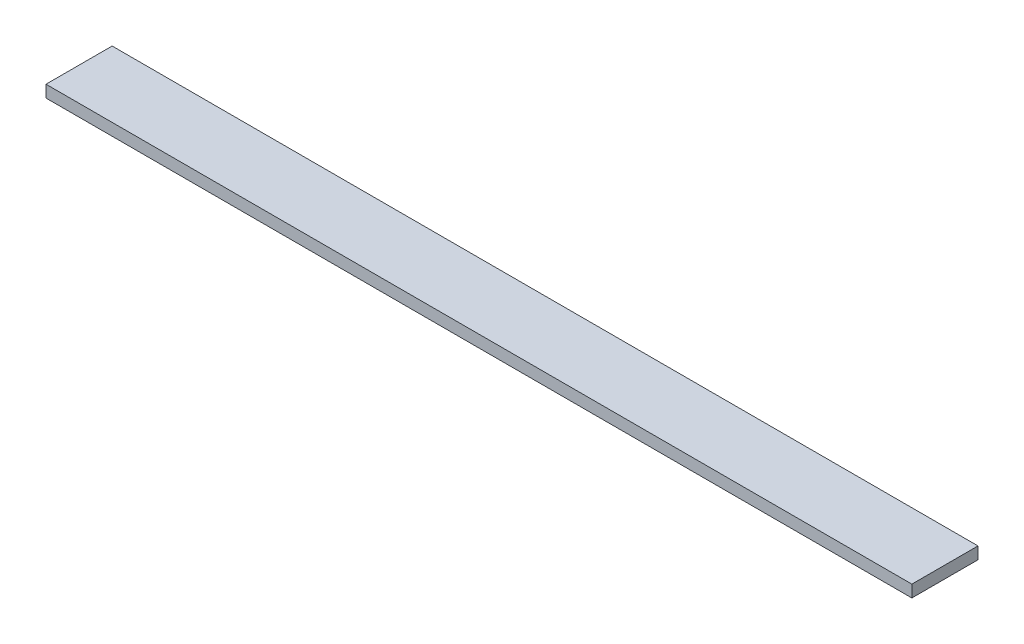
SolidWorks part; units mm, degrees
material "PVC Rigid"
ref_plane "Frontal Plane" through (0, 0, 0) normal (0, 0, 1) x (1, 0, 0)
ref_plane "Horizontal Plane" through (0, 0, 0) normal (0, 1, 0) x (1, 0, 0)
ref_plane "Profile Plane" through (0, 0, 0) normal (1, 0, 0) x (0, 0, -1)
sketch "Sketch1" plane through (0, 0, 0) normal (0, 1, 0) x (1, 0, 0)
  line L1 (-914.4, -69.85) -> (914.4, -69.85)
  line L2 (-914.4, -69.85) -> (-914.4, 69.85)
  line L3 (-914.4, 69.85) -> (914.4, 69.85)
  line L4 (914.4, -69.85) -> (914.4, 69.85)
  line L5 (-914.4, -69.85) -> (914.4, 69.85) construction
  line L6 (-914.4, 69.85) -> (914.4, -69.85) construction
  point P0 (0, 0)
  dimension "D1" = 139.7
  dimension "D2" = 1828.8
extrude "Boss-Extrude1" add sketch "Sketch1" along normal blind 25.4
sketch "Sketch2" plane through (0, 25.4, 0) normal (0, 1, 0) x (1, 0, 0)
  line L0 (-784.4, 69.85) -> (-784.4, -80.15)
  line L1 (914.4, 69.85) -> (-914.4, 69.85) construction
  line L2 (-784.4, -80.15) -> (914.4, -80.15)
  line L3 (914.4, -69.85) -> (914.4, 69.85) construction
  line L4 (914.4, -80.15) -> (914.4, 69.85)
  line L5 (914.4, 69.85) -> (-784.4, 69.85)
  line L6 (-914.4, 69.85) -> (-914.4, -69.85) construction
  dimension "D1" = 130
  dimension "D2" = 150
extrude "Cut-Extrude1" [suppressed] cut sketch "Sketch2" against normal through all
sketch "Sketch3" [suppressed] plane through (0, 12.7, 0) normal (0, 1, 0) x (1, 0, 0)
  line L0 (-720, 155) -> (-850, 155) construction
  line L1 (-830, 135) -> (-740, 135)
  line L2 (-830, 135) -> (-830, 5)
  line L3 (-830, 5) -> (-740, 5)
  line L4 (-740, 135) -> (-740, 5)
  line L5 (-830, 135) -> (-740, 5) construction
  line L6 (-830, 5) -> (-740, 135) construction
  line L7 (-850, 155) -> (-850, -155) construction
  line L8 (-720, 155) -> (-720, 5) construction
  line L9 (-720, 5) -> (850, 5) construction
  point P0 (-785, 70)
  dimension "D1" = 20
  dimension "D2" = 20
  dimension "D3" = 20
extrude "Cut-Extrude2" [suppressed] cut sketch "Sketch3" against normal offset from surface (5 mm away) 5 up to face at (0, 0, 0)
sketch "Sketch4" plane through (0, 25.4, 0) normal (0, 1, 0) x (1, 0, 0)
  line L0 (-914.4, -69.85) -> (914.4, -69.85) construction
  line L1 (768, 38.45) -> (812, 38.45) construction
  line L2 (0, 219.5854) -> (0, -221.9562) construction
  line L3 (-837.5, -19.05) -> (-757.5, -19.05) construction
  line L4 (757.5, 8.45) -> (822.5, 8.45) construction
  circle A0 centre (-757.5, 8.45) radius 2.5
  circle A1 centre (-822.5, 8.45) radius 2.5
  circle A2 centre (-822.5, -46.55) radius 2.5
  circle A3 centre (-757.5, -46.55) radius 2.5
  circle A4 centre (822.5, -46.55) radius 2.5
  circle A5 centre (822.5, 8.45) radius 2.5
  circle A6 centre (757.5, -46.55) radius 2.5
  circle A7 centre (757.5, 8.45) radius 2.5
  circle A8 centre (768, 38.45) radius 1.25
  circle A9 centre (812, 38.45) radius 1.25
  point P27 (790, 38.45)
  point P28 (790, 8.45)
  dimension "D1" = 5
  dimension "D8" = 2.5
  dimension "D2" = 65
  dimension "D3" = 55
  dimension "D5" = 757.5
  dimension "D4" = 27.5
  dimension "D6" = 50.8
  dimension "D7" = 30
  dimension "D9" = 44
extrude "Cut-Extrude3" [suppressed] cut sketch "Sketch4" against normal blind 10
equation "\"BaseL\"= 6ft"
equation "\"BaseW\"= 5.5in"
equation "\"SlidePlateL\"= 8cm"
equation "\"SlidePlateW\"= 11cm"
equation "\"SlidePlateThickness\"= 5mm"
equation "\"PlateGap\"= 1cm"
equation "\"D1@Sketch1\"=\"BaseW\""
equation "\"D2@Sketch1\"=\"BaseL\""
equation "\"BaseThickness\"= 1in"
equation "\"D1@Boss-Extrude1\"=\"BaseThickness\""
equation "\"D4@Sketch4\"=\"D3@Sketch4\"/2"
